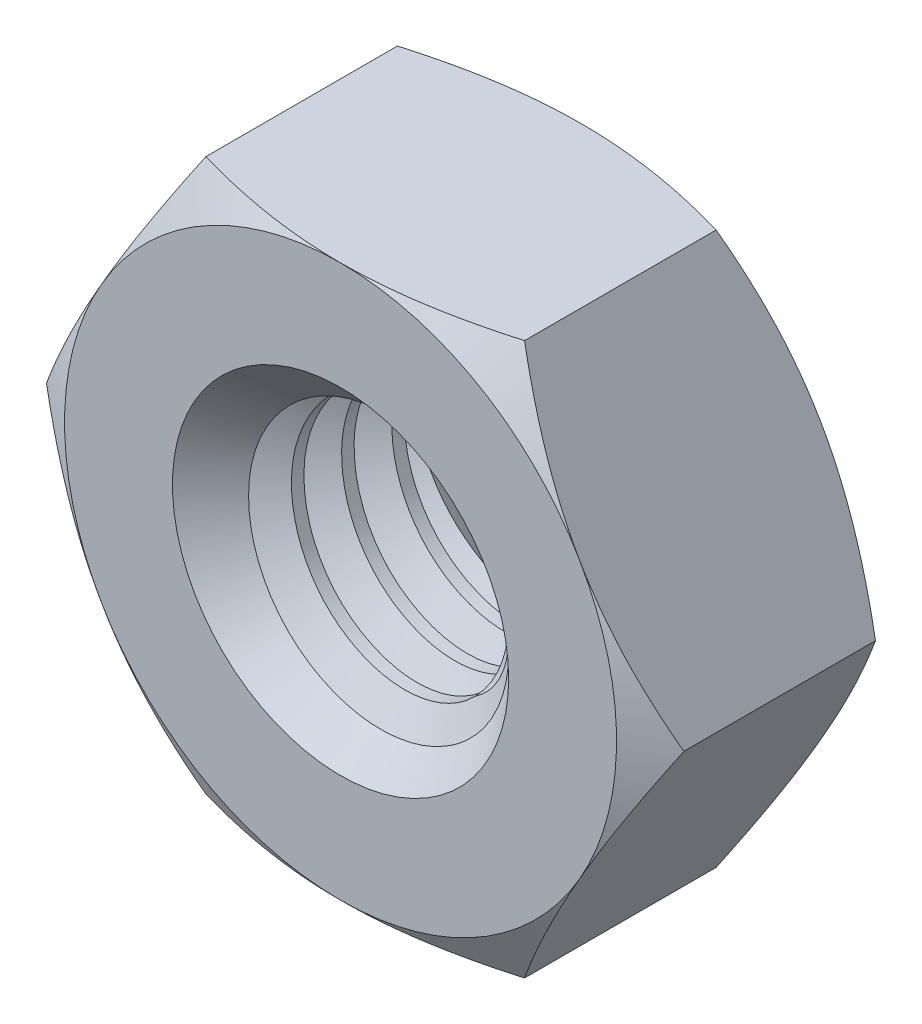
SolidWorks part; units mm, degrees
ref_plane "Front" through (0, 0, 0) normal (0, 0, 1) x (1, 0, 0)
ref_plane "Top" through (0, 0, 0) normal (0, 1, 0) x (1, 0, 0)
ref_plane "Right" through (0, 0, 0) normal (1, 0, 0) x (0, 0, -1)
sketch "Çizim1" plane through (0, 0, 0) normal (0, 0, 1) x (1, 0, 0)
  line L1 (3.1754, 0) -> (1.5877, 2.75)
  line L2 (1.5877, 2.75) -> (-1.5877, 2.75)
  line L3 (-1.5877, 2.75) -> (-3.1754, 0)
  line L4 (-3.1754, 0) -> (-1.5877, -2.75)
  line L5 (-1.5877, -2.75) -> (1.5877, -2.75)
  line L6 (1.5877, -2.75) -> (3.1754, 0)
  circle A0 centre (0, 0) radius 2.75 construction
  point P1 (0, 0)
  dimension "D1" = 5.5
extrude "Yükseklik-Ekstrüzyon1" add sketch "Çizim1" along normal blind 2.4
sketch "Çizim2" plane through (0, 0, 2.4) normal (0, 0, 1) x (1, 0, 0)
  circle A0 centre (0, 0) radius 2.75
extrude "Kes-Ekstrüzyon1" cut sketch "Çizim2" against normal blind 2.4 draft 60 flip side to cut
sketch "Çizim3" plane through (0, 0, 0) normal (0, 0, -1) x (-1, 0, 0)
  circle A0 centre (0, 0) radius 2.75
extrude "Kes-Ekstrüzyon2" cut sketch "Çizim3" against normal blind 2.4 draft 60 flip side to cut
sketch "Çizim4" plane through (0, 0, 0) normal (0, 0, -1) x (-1, 0, 0)
  circle A0 centre (0, 0) radius 1.175
  dimension "D1" = 2.35
extrude "Kes-Ekstrüzyon3" cut sketch "Çizim4" against normal blind 2.4
chamfer "Pah1" distance 0.5 angle 45 2 edges at (-1.175, 0, 2.4) (-1.175, 0, 0)
sketch "Çizim5" plane through (0, 0, 2.4) normal (0, 0, 1) x (1, 0, 0)
  circle A0 centre (0, 0) radius 1.175
curve "Helis/Spiral1" pitch 0.5 height 3 radius 1.175 centre (0, 0, 2.4) axis (0, 0, -1) start towards (-1, 0, 0)
ref_plane "Düzlem1" through (-1.175, 0, -0.6) normal (0, 0.9977, -0.0676) x (1, 0, 0)
sketch "Çizim6" plane through (-1.175, 0, -0.6) normal (0, 0.9977, -0.0676) x (1, 0, 0)
  line L1 (-0.325, 0) -> (0.0987, -0.2446)
  line L3 (0.0987, 0.2446) -> (-0.325, 0)
  line L4 (0.0987, 0.2446) -> (0.0987, -0.2446)
  line L5 (0.1625, 0) -> (0.1625, 0.2815) [skipped]
  circle A0 centre (0, 0) radius 0.1625 construction
  dimension "D1" = 0.325
sweep "Kes-Süpür1" cut profiles "Çizim6" path "Helis/Spiral1" align with end faces yes
